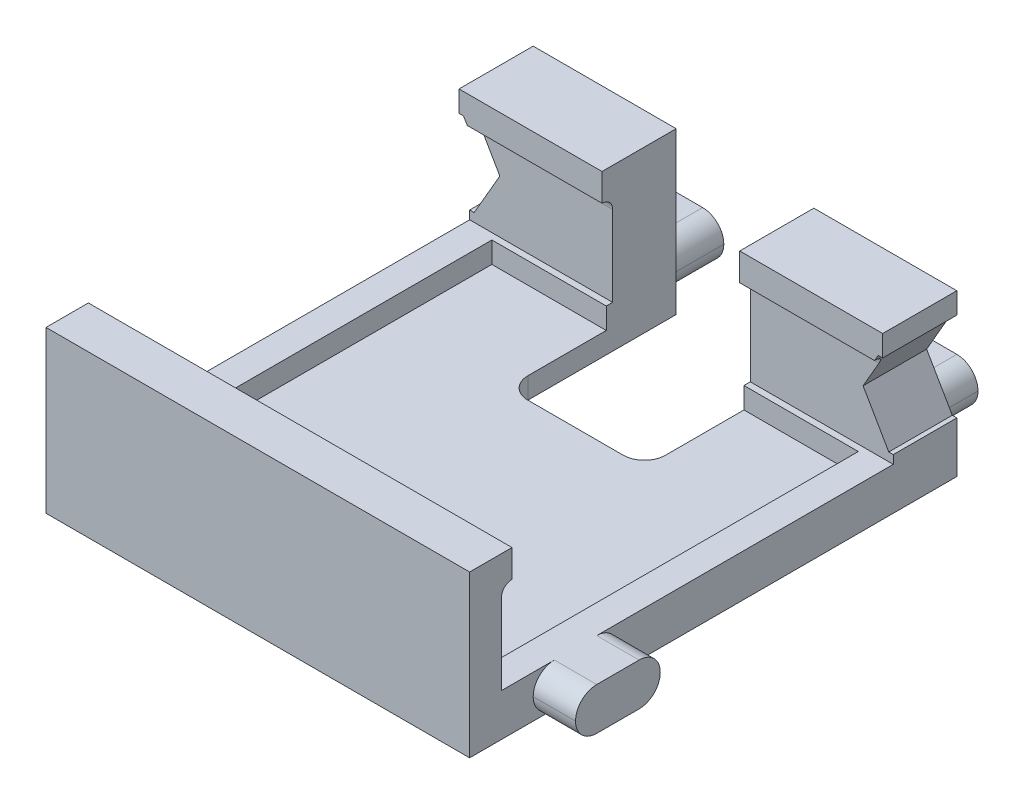
SolidWorks part; units mm, degrees
ref_plane "Front Plane" through (0, 0, 0) normal (0, 0, 1) x (1, 0, 0)
ref_plane "Top Plane" through (0, 0, 0) normal (0, 1, 0) x (1, 0, 0)
ref_plane "Right Plane" through (0, 0, 0) normal (1, 0, 0) x (0, 0, -1)
sketch "Sketch1" plane through (0, 0, 0) normal (0, 1, 0) x (1, 0, 0)
  line L0 (0, 11.5) -> (0, -11.5) construction
  line L1 (10, 11.5) -> (-10, 11.5)
  line L2 (10, 11.5) -> (10, -11.5)
  line L3 (10, -11.5) -> (-10, -11.5)
  line L4 (-10, 11.5) -> (-10, -11.5)
  line L5 (10, 11.5) -> (-10, -11.5) construction
  line L6 (10, -11.5) -> (-10, 11.5) construction
  line L15 (10, -8.5) -> (10, -4.5)
  line L21 (-3.25, 3.5) -> (3.25, 3.5)
  line L22 (-10, -8.5) -> (-12, -8.5)
  line L23 (-10, -8.5) -> (-10, -4.5)
  line L24 (-10, -4.5) -> (-12, -4.5)
  line L25 (-12, -8.5) -> (-12, -4.5)
  line L26 (10, -8.5) -> (12, -8.5)
  line L27 (12, -8.5) -> (12, -4.5)
  line L28 (10, -4.5) -> (12, -4.5)
  line L29 (-3.25, 3.5) -> (-3.25, 11.5)
  line L30 (-3.25, 11.5) -> (3.25, 11.5)
  line L31 (3.25, 3.5) -> (3.25, 11.5)
  line L32 (-3.25, 3.5) -> (3.25, 11.5) construction
  line L33 (-3.25, 11.5) -> (3.25, 3.5) construction
  line L41 (-6, 14.5) -> (-6, 11.5) construction
  line L42 (-4, 11.5) -> (-8, 11.5)
  line L43 (-4, 11.5) -> (-4, 14.5)
  line L44 (-4, 14.5) -> (-8, 14.5)
  line L45 (-8, 11.5) -> (-8, 14.5)
  line L46 (4, 11.5) -> (8, 11.5)
  line L47 (8, 11.5) -> (8, 14.5)
  line L48 (4, 14.5) -> (8, 14.5)
  line L49 (4, 11.5) -> (4, 14.5)
  point P0 (0, 0)
  point P14 (0, 7.5)
  dimension "D1" = 20
  dimension "D2" = 23
  dimension "D3" = 2
  dimension "D4" = 4
  dimension "D5" = 3
  dimension "D6" = 6.5
  dimension "D7" = 8
  dimension "D8" = 12
  dimension "D9" = 3
extrude "Boss-Extrude1" add sketch "Sketch1" along normal blind 2 contours L23 L4 | L1 L4 L3 L2 | L2 L15 | L31 L21 L29 L1 | L43 L1 | L1 region at (0, 0, 0.9559) region at (6, 0, -13) region at (11, 0, 6.5) region at (-6, 0, -13) region at (-11, 0, 6.5)
fillet "Fillet1" radius 1 18 edges at (11, 0, 4.5) (11, 2, 4.5) (11, 0, 8.5) (11, 2, 8.5) (-11, 0, 4.5) (-11, 2, 4.5) (-11, 0, 8.5) (-11, 2, 8.5) (-3.25, 1, -3.5) (3.25, 1, -3.5) (-8, 2, -13) (-8, 0, -13) (4, 0, -13) (4, 2, -13) (-4, 2, -13) (-4, 0, -13) (8, 0, -13) (8, 2, -13)
sketch "Sketch4" plane through (0, 2, 0) normal (0, 1, 0) x (1, 0, 0)
  line L0 (0, 5.3573) -> (0, -4.2859) construction
  line L2 (-8.65, 8.2) -> (8.65, 8.2)
  line L3 (-8.65, 8.2) -> (-8.65, -9.5)
  line L4 (-8.65, -9.5) -> (8.65, -9.5)
  line L5 (8.65, 8.2) -> (8.65, -9.5)
  line L6 (-8.65, 8.2) -> (8.65, -9.5) construction
  line L7 (-8.65, -9.5) -> (8.65, 8.2) construction
  line L10 (10, -11.5) -> (-10, -11.5) construction
  point P1 (0, -0.65)
  dimension "D1" = 17.3
  dimension "D2" = 2
  dimension "D3" = 17.7
extrude "Cut-Extrude3" cut sketch "Sketch4" against normal blind 1
sketch "Sketch5" plane through (10, 0, 0) normal (1, 0, 0) x (0, 0, -1)
  line L0 (8.2, 1) -> (-9.5, 1) construction
  line L1 (8.2, 1) -> (-9.5, 1)
  line L3 (-11.5, 2) -> (-10, 2)
  line L4 (-11.5, 2) -> (-11.5, 6.3)
  line L5 (-11.5, 6.3) -> (-10, 6.3)
  line L6 (-10, 2) -> (-10, 6.3)
  line L7 (11.5, 2) -> (8.5, 2)
  line L8 (11.5, 2) -> (11.5, 6.3)
  line L9 (11.5, 6.3) -> (8.5, 6.3)
  line L10 (8.5, 2) -> (8.5, 6.3)
  line L11 (-11.5, 6.3) -> (-9.5, 6.3)
  line L12 (-11.5, 6.3) -> (-11.5, 7.6)
  line L13 (-11.5, 7.6) -> (-9.5, 7.6)
  line L14 (-9.5, 6.3) -> (-9.5, 7.6)
  line L15 (11.5, 6.3) -> (8, 6.3)
  line L16 (11.5, 6.3) -> (11.5, 7.6)
  line L17 (11.5, 7.6) -> (8, 7.6)
  line L18 (8, 6.3) -> (8, 7.6)
  line M18 (-7.5, 2) -> (-11.5, 2)
  dimension "D1" = 1.5
  dimension "D2" = 5.3
  dimension "D3" = 18.5
  dimension "D4" = 1.3
  dimension "D5" = 0.5
  dimension "D6" = 0.5
extrude "Boss-Extrude3" add sketch "Sketch5" against normal up to surface (20 mm away) contours L6 L5 L4 M18 | L11 L14 L13 L12 L5 | L18 L15 L9 L16 L17 | L10 L7 L8 L9 region at (10, 4.15, 10.75) region at (10, 6.95, 10.5) region at (10, 4.15, -10) region at (10, 6.95, -9.75) up to face at (-10, 1, -1.5828)
sketch "Sketch7" plane through (0, 7.6, 0) normal (0, 1, 0) x (1, 0, 0)
  line L0 (3.25, 4.5) -> (3.25, 11.5) construction
  line L1 (-3.25, 11.5) -> (3.25, 11.5)
  line L2 (-3.25, 11.5) -> (-3.25, 8)
  line L3 (-3.25, 8) -> (3.25, 8)
  line L4 (3.25, 11.5) -> (3.25, 8)
  line L5 (-10, 8) -> (10, 8) construction
  line L11 (0, 5.6258) -> (0, -4.3103) construction
extrude "Cut-Extrude5" cut sketch "Sketch7" against normal up to next
sketch "Sketch8" plane through (0, 0, -11.5) normal (0, 0, -1) x (-1, 0, 0)
  line L0 (-3.25, 7.6) -> (-10, 7.6) construction
  line L1 (-8.5751, 4.5) -> (-9.7876, 6.6)
  line L2 (-9.7876, 6.6) -> (-12.2124, 6.6)
  line L3 (-12.2124, 6.6) -> (-13.4249, 4.5)
  line L4 (-13.4249, 4.5) -> (-12.2124, 2.4)
  line L5 (-12.2124, 2.4) -> (-9.7876, 2.4)
  line L6 (-9.7876, 2.4) -> (-8.5751, 4.5)
  line L7 (0, 12.0608) -> (0, -4.099) construction
  line L8 (12.2124, 2.4) -> (9.7876, 2.4)
  line L9 (13.4249, 4.5) -> (12.2124, 2.4)
  line L10 (12.2124, 6.6) -> (13.4249, 4.5)
  line L11 (9.7876, 6.6) -> (12.2124, 6.6)
  line L12 (8.5751, 4.5) -> (9.7876, 6.6)
  line L13 (9.7876, 2.4) -> (8.5751, 4.5)
  circle A0 centre (-11, 4.5) radius 2.1 construction
  dimension "D1" = 3.1
  dimension "D2" = 22
  dimension "D3" = 4.2
extrude "Cut-Extrude6" cut sketch "Sketch8" against normal blind 3.5
fillet "Fillet3" radius 0.5 3 edges at (6.4322, 6.3, -8.5) (-6.4322, 6.3, -8.5) (0, 6.3, 10)
